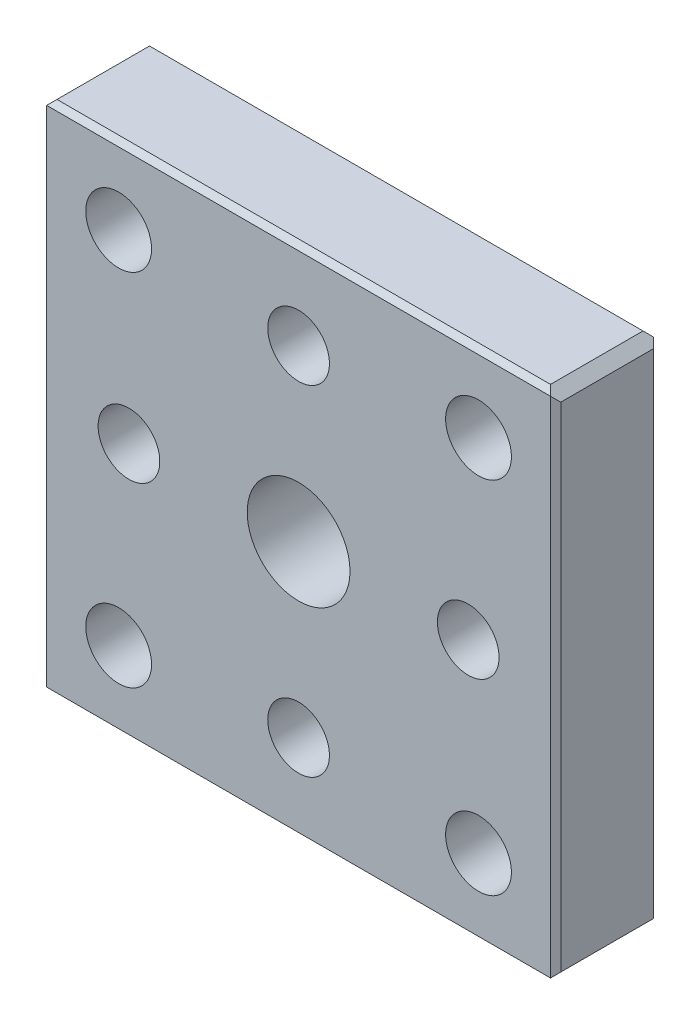
SolidWorks part; units mm, degrees
material "Plain Carbon Steel"
ref_plane "Front Plane" through (0, 0, 0) normal (0, 0, 1) x (1, 0, 0)
ref_plane "Top Plane" through (0, 0, 0) normal (0, 1, 0) x (1, 0, 0)
ref_plane "Right Plane" through (0, 0, 0) normal (1, 0, 0) x (0, 0, -1)
sketch "Sketch1" plane through (0, 0, 0) normal (0, 0, 1) x (1, 0, 0)
  line L1 (-25, -25) -> (25, -25)
  line L2 (-25, -25) -> (-25, 25)
  line L3 (-25, 25) -> (25, 25)
  line L4 (25, -25) -> (25, 25)
  line L5 (-25, -25) -> (25, 25) construction
  line L6 (-25, 25) -> (25, -25) construction
  point P0 (0, 0)
  dimension "D1" = 50
  dimension "D2" = 50
extrude "Boss-Extrude1" add sketch "Sketch1" along normal mid plane 10
hole_wizard "M6 Clearance Hole1" positions "Sketch4" profile "Sketch3" hole size "M6" standard "ISO" end condition through all
sketch "Sketch4" plane through (0, 0, 5) normal (0, 0, 1) x (1, 0, 0)
  line L0 (-25, 0) -> (25, 0) construction
  line L1 (-25, 25) -> (-25, -25) construction
  line L2 (25, -25) -> (25, 25) construction
  line L4 (0, 25) -> (0, -25) construction
  line L5 (25, 25) -> (-25, 25) construction
  line L6 (-25, -25) -> (25, -25) construction
  point P0 (-17.5, 17.5)
  point P2 (17.5, 17.5)
  point P4 (17.5, -17.5)
  point P6 (-17.5, -17.5)
  dimension "D1" = 35
  dimension "D2" = 35
sketch "Sketch3" plane through (-17.5, 17.5, 5) normal (1, 0, 0) x (0, -1, 0)
  line L0 (0, 0) -> (0, 10)
  line L1 (0, 10) -> (3.2, 10)
  line L2 (3.2, 10) -> (3.2, 0)
  line L5 (3.2, 0) -> (0, 0)
  line L11 (0, -6.35) -> (0, 107.95) construction
  dimension "Thru Hole Dia." = 6.4
  dimension "Thru Hole Depth" = 10
sketch "Sketch5" plane through (0, 0, 5) normal (0, 0, 1) x (1, 0, 0)
  circle A0 centre (0, 0) radius 5
  dimension "D1" = 10
extrude "Cut-Extrude1" cut sketch "Sketch5" against normal up to next
sketch "Sketch6" plane through (0, 0, -5) normal (0, 0, -1) x (-1, 0, 0)
  circle A0 centre (0, 0) radius 19
  dimension "D1" = 38
chamfer "Chamfer1" distance 1 angle 45 4 edges at (25, -25, 0) (-25, -25, 0) (-25, 25, 0) (25, 25, 0)
chamfer "Chamfer2" distance 0.5 angle 45 8 edges at (0, -25, 5) (0, -25, -5) (0, 25, -5) (0, 25, 5) (25, 0, -5) (25, 0, 5) (-25, 0, -5) (-25, 0, 5)
hole_wizard "Ø6.0 (6) Diameter Hole1" positions "Sketch9" profile "Sketch8" hole size "Ø6.0" standard "ISO" end condition through all
sketch "Sketch9" plane through (0, 0, -5) normal (0, 0, -1) x (-1, 0, 0)
  point P0 (-16.5, 0)
  point P3 (0, 16.5)
  point P6 (16.5, 0)
  point P9 (0, -16.5)
sketch "Sketch8" plane through (16.5, 0, -5) normal (1, 0, 0) x (0, 1, 0)
  line L0 (0, 0) -> (0, 10)
  line L1 (0, 10) -> (3, 10)
  line L2 (3, 10) -> (3, 0)
  line L5 (3, 0) -> (0, 0)
  line L11 (0, -6.35) -> (0, 107.95) construction
  dimension "Thru Hole Dia." = 6
  dimension "Thru Hole Depth" = 10
sketch "Sketch12" plane through (0, 0, -5) normal (0, 0, -1) x (-1, 0, 0)
  circle A1 centre (16.5, 0) radius 6.25 construction
  circle A3 centre (0, -16.5) radius 6.25 construction
  circle A5 centre (-16.5, 0) radius 6.25 construction
  circle A7 centre (0, 16.5) radius 6.25 construction
  circle A9 centre (16.5, 0) radius 6.25
  circle A11 centre (0, -16.5) radius 6.25
  circle A13 centre (-16.5, 0) radius 6.25
  circle A15 centre (0, 16.5) radius 6.25
extrude "Cut-Extrude2" cut sketch "Sketch12" against normal blind 3
